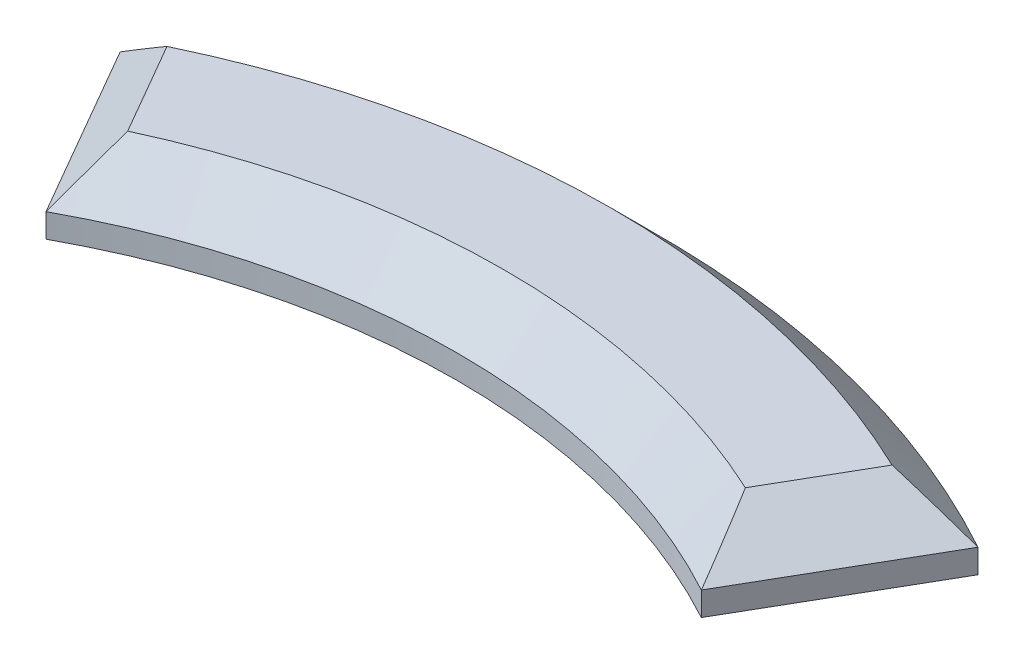
SolidWorks part; units mm, degrees
ref_plane "Front Plane" through (0, 0, 0) normal (0, 0, 1) x (1, 0, 0)
ref_plane "Top Plane" through (0, 0, 0) normal (0, 1, 0) x (1, 0, 0)
ref_plane "Right Plane" through (0, 0, 0) normal (1, 0, 0) x (0, 0, -1)
sketch "Sketch1" plane through (0, 0, 0) normal (0, 1, 0) x (1, 0, 0)
  line L0 (-14, 24.2487) -> (-19, 32.909) construction
  line L1 (14, 24.2487) -> (19, 32.909) construction
  line L2 (0, 0) -> (4, 0) construction
  line L3 (-17.9717, 32.6279) -> (-13.7293, 25.2798)
  line L4 (17.9717, 32.6279) -> (13.7293, 25.2798)
  line L5 (-16.5, 28.5788) -> (-15.8505, 28.9538) construction
  line L6 (15.8505, 28.9538) -> (16.5, 28.5788) construction
  circle A0 centre (0, 0) radius 28 construction
  circle A1 centre (0, 0) radius 38 construction
  arc A2 (-17.9717, 32.6279) -> (17.9717, 32.6279) centre (0, 0) cw
  arc A3 (-13.7293, 25.2798) -> (13.7293, 25.2798) centre (0, 0) cw
  point P17 (12, 14)
  point P18 (10, 12)
  point P19 (16.5, 28.5788)
  point P20 (0, 0)
  dimension "D1" = 28
  dimension "D2" = 38
  dimension "D4" = 0.75
  dimension "D6" = 60
  dimension "D3" = 60
  dimension "D5" = 0.75
extrude "Boss-Extrude1" add sketch "Sketch1" along normal blind 3
chamfer "Chamfer1" distance 2 angle 45 4 edges at (15.8505, 3, -28.9538) (0, 3, -37.25) (0, 3, -28.7673) (-15.8505, 3, -28.9538)
sketch "Sketch2" plane through (0, 0, 0) normal (0, -1, 0) x (1, 0, 0)
  line L0 (0, -37.25) -> (0, -28.7673) construction
  arc A0 (-17.9717, -32.6279) -> (17.9717, -32.6279) centre (0, 0) ccw construction
  arc A1 (-13.7293, -25.2798) -> (13.7293, -25.2798) centre (0, 0) ccw construction
  circle A2 centre (0, -33.0087) radius 1.625
  dimension "D1" = 3.25
extrude "Cut-Extrude1" cut sketch "Sketch2" against normal blind 2
